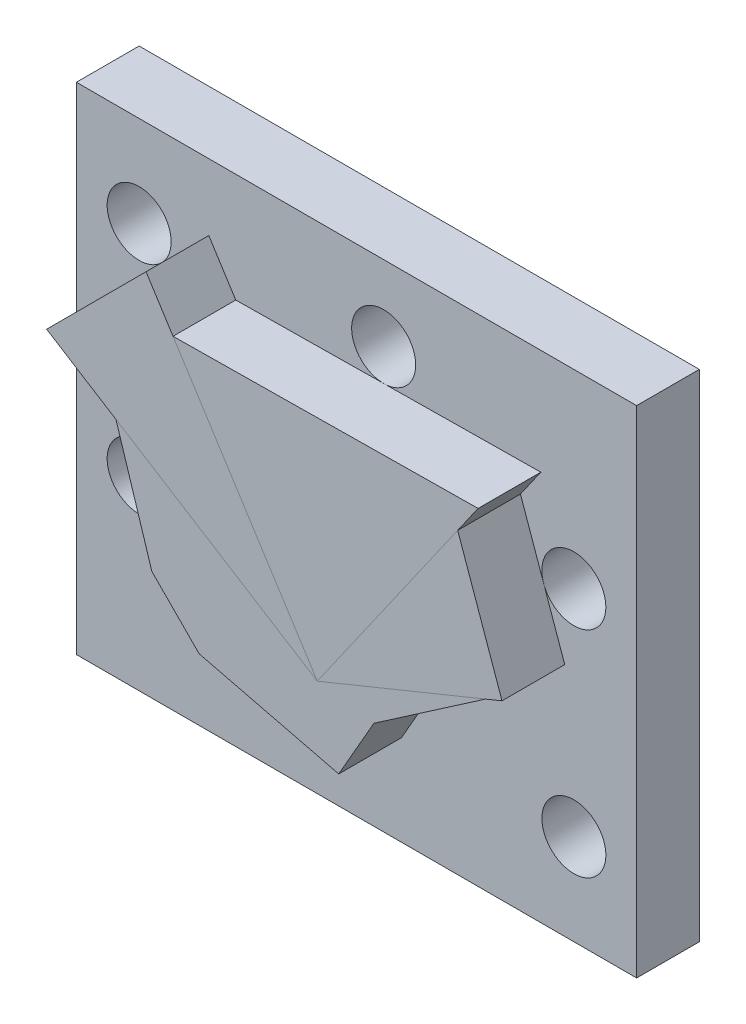
SolidWorks part; units mm, degrees
other "Tri-A"
ref_plane "Front Plane" through (0, 0, 0) normal (0, 0, 1) x (1, 0, 0)
ref_plane "Top Plane" through (0, 0, 0) normal (0, 1, 0) x (1, 0, 0)
ref_plane "Right Plane" through (0, 0, 0) normal (1, 0, 0) x (0, 0, -1)
sketch "Sketch1" plane through (0, 0, 0) normal (0, 0, 1) x (1, 0, 0)
  line L0 (-48.9659, -67.0038) -> (40.3161, -66.9968)
  line L1 (-48.9659, -67.0038) -> (-48.9721, 11.9962)
  line L2 (40.3161, -66.9968) -> (40.31, 12.0032)
  line L3 (-48.9721, 11.9962) -> (40.31, 12.0032)
  line L4 (-48.9659, -67.0038) -> (40.31, 12.0032) construction
  line L5 (40.3161, -66.9968) -> (-48.9721, 11.9962) construction
  line L6 (30.315, -52.4976) -> (-38.9709, -2.503) construction
  circle A3 centre (0, 0) radius 5.1
  circle A6 centre (30.3123, -18.2661) radius 5.1
  circle A10 centre (30.315, -52.4976) radius 5.1
  circle A15 centre (-8.656, -55.0007) radius 5.1
  circle A20 centre (-38.9682, -37.503) radius 5.1
  circle A23 centre (-38.9709, -2.503) radius 5.1
  point P0 (-4.328, -27.5003)
  point P1 (-4.328, -27.5003)
  dimension "D7" = 12
  dimension "D8" = 10
  dimension "D9" = 10
extrude "Adapt" add sketch "Sketch1" against normal blind 10
sketch "Sketch2" [suppressed] plane through (0, 0, 0) normal (0, 0, 1) x (1, 0, 0)
  line L0 (-7.4842, -19.0571) -> (4.6797, -27.8343)
  line L1 (-7.4842, -19.0571) -> (-13.3357, -27.1664)
  line L2 (4.6797, -27.8343) -> (-1.1717, -35.9436)
  line L3 (-13.3357, -27.1664) -> (-1.1717, -35.9436)
  line L4 (-7.4842, -19.0571) -> (-1.1717, -35.9436) construction
  line L5 (4.6797, -27.8343) -> (-13.3357, -27.1664) construction
  line L7 (30.315, -52.4976) -> (-38.9709, -2.503) construction
  point P1 (-4.328, -27.5003)
  dimension "D1" = 15
  dimension "D2" = 10
extrude "Cut-Extrude1" [suppressed] cut sketch "Sketch2" against normal up to next
sketch "Sketch4" plane through (0, 0, 0) normal (0, 0, 1) x (1, 0, 0)
  line L0 (-19.4106, -47.1067) -> (2.8363, -52.5725)
  line L1 (2.8363, -52.5725) -> (8.4467, -42.7723)
  line L2 (8.4467, -42.7723) -> (26.2367, -30.5382)
  line L3 (26.2367, -30.5382) -> (-0.582, -41.4757)
  line L4 (-0.582, -41.4757) -> (-32.668, -21.3851)
  line L5 (-32.668, -21.3851) -> (-26.9478, -39.5066)
  line L6 (-26.9478, -39.5066) -> (-19.4106, -47.1067)
  line L7 (-0.582, -41.4757) -> (-43.7167, -14.4669)
  line L8 (-43.7167, -14.4669) -> (-27.8734, 1.3869)
  line L9 (-27.8734, 1.3869) -> (-0.582, -41.4757)
  line L10 (-0.582, -41.4757) -> (25.0503, -4.8161)
  line L11 (25.0503, -4.8161) -> (-23.5726, -5.3678)
  line L12 (-23.5726, -5.3678) -> (-0.582, -41.4757)
  line L13 (-0.582, -41.4757) -> (21.7988, -9.4664)
  line L14 (21.7988, -9.4664) -> (28.8574, -29.4694)
  line L15 (28.8574, -29.4694) -> (-0.582, -41.4757)
  line L16 (-38.9709, -2.503) -> (22.422, -63.8554) construction
  line L17 (0, 0) -> (0.7147, -62.9909) construction
  line L18 (30.3123, -18.2661) -> (-38.9888, -42.7207) construction
  line L19 (5.8053, 3.8601) -> (-8.656, -55.0007) construction
  circle A0 centre (-8.656, -55.0007) radius 5.1 construction
  circle A1 centre (-38.9709, -2.503) radius 5.1 construction
  circle A2 centre (-8.656, -55.0007) radius 5.1 construction
  circle A3 centre (0, 0) radius 5.1 construction
  circle A4 centre (30.3123, -18.2661) radius 5.1 construction
  circle A5 centre (30.3123, -18.2661) radius 5.1 construction
  circle A6 centre (-38.9709, -2.503) radius 5.1 construction
  point P15 (0, 0)
  point P19 (-13.3567, -46.1341)
  point P28 (-2.9352, -26.5879)
  point P29 (22.422, -63.8554)
  point P30 (0.7147, -62.9909)
  point P31 (5.8053, 3.8601)
  point P32 (-26.9478, -39.5066)
  point P34 (8.4467, -42.7723)
  point P37 (28.8574, -29.4694)
extrude "Base-Tri" add sketch "Sketch4" along normal blind 10 separate body contours L5 L6 L0 L1 L2 L3 L4 region at (-10.5539, -39.7045, 0)
extrude "Tria-A" add sketch "Sketch4<3>" along normal blind 10 separate body contours L9 L8 L7 L4 region at (-24.0574, -18.1852, 0)
sketch "Sketch4<3>" plane through (0, 0, 0) normal (0, 0, 1) x (1, 0, 0) same geometry as "Sketch4"
extrude "Tria-B" add sketch "Sketch4<4>" along normal blind 10 separate body contours L10 L11 L9 region at (0.2986, -17.2198, 0)
sketch "Sketch4<4>" plane through (0, 0, 0) normal (0, 0, 1) x (1, 0, 0) same geometry as "Sketch4"
extrude "Tria-C" add sketch "Sketch4<5>" along normal blind 10 separate body contours L15 L14 L10 L3 region at (16.6914, -26.8038, 0)
sketch "Sketch4<5>" plane through (0, 0, 0) normal (0, 0, 1) x (1, 0, 0) same geometry as "Sketch4"
